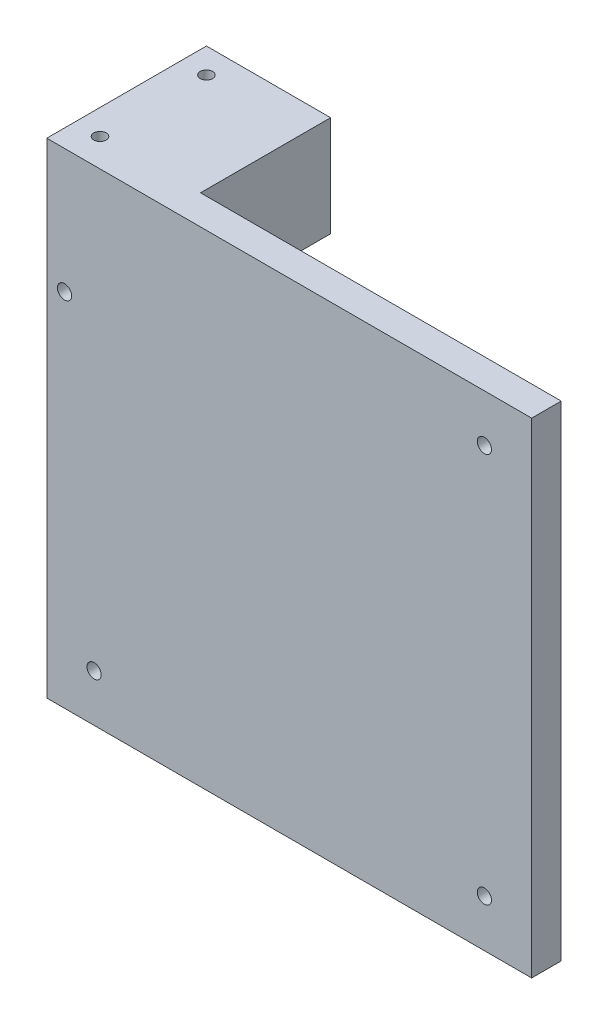
SolidWorks part; units mm, degrees
ref_plane "前基準面" through (0, 0, 0) normal (0, 0, 1) x (1, 0, 0)
ref_plane "上基準面" through (0, 0, 0) normal (0, 1, 0) x (1, 0, 0)
ref_plane "右基準面" through (0, 0, 0) normal (1, 0, 0) x (0, 0, -1)
ref_axis "基準軸1" through (0, -55, 0) along (0, 1, 0)
ref_axis "基準軸2" through (-88.99, 0, 0) along (1, 0, 0)
ref_axis "基準軸3" through (0, 0, 55) along (0, 0, -1)
sketch "草圖1" plane through (0, 0, 0) normal (0, 0, 1) x (1, 0, 0)
  line L0 (0, -55) -> (0, 55) construction
  line L1 (-41, -41) -> (41, -41)
  line L2 (-41, -41) -> (-41, 41)
  line L3 (-41, 41) -> (41, 41)
  line L4 (41, -41) -> (41, 41)
  line L5 (55, 0) -> (-55, 0) construction
  circle A0 centre (0, 0) radius 35.5
  point P7 (0, -41)
  point P10 (41, 0)
  dimension "D1" = 71
  dimension "D2" = 82
  dimension "D3" = 82
extrude "填料-伸長1" add sketch "草圖1" along normal blind 245
sketch "草圖2" plane through (0, 0, 0) normal (0, 0, -1) x (-1, 0, 0)
  line L1 (-41, 41) -> (41, 41)
  line L2 (-41, 41) -> (-41, -41)
  line L3 (-41, -41) -> (41, -41)
  line L4 (41, 41) -> (41, -41)
extrude "填料-伸長2" add sketch "草圖2" along normal blind 27
ref_plane "平面1" through (0, 0, -13.5) normal (0, 0, -1) x (-1, 0, 0)
sketch "草圖3" plane through (0, 0, 245) normal (0, 0, 1) x (1, 0, 0)
  line L0 (-41, 41) -> (-41, -41) construction
  line L1 (-41, 10) -> (-33, 10)
  line L2 (-41, 10) -> (-41, -10)
  line L3 (-41, -10) -> (-33, -10)
  line L4 (-33, 10) -> (-33, -10)
  line L6 (55, 0) -> (-55, 0) construction
  point P6 (-33, 0)
  dimension "D1" = 8
  dimension "D2" = 20
extrude "除料-伸長1" cut sketch "草圖3" against normal up to surface (245 mm away) up to face at (35.5, 0, 0)
sketch "草圖4" plane through (0, 0, 245) normal (0, 0, 1) x (1, 0, 0)
  line L1 (41, 41) -> (-41, 41) construction
  line L2 (-41, 41) -> (-41, 10) construction
  line L3 (-41, -41) -> (41, -41) construction
  line L4 (-41, -10) -> (-41, -41) construction
  circle A0 centre (-32.9, 33) radius 4
  circle A1 centre (33.1, 32.9) radius 4
  circle A2 centre (33, -33.1) radius 4
  circle A3 centre (-33, -33) radius 4
  point P15 (0.05, -0.05)
  dimension "D1" = 8
  dimension "D5" = 8
  dimension "D2" = 8
  dimension "D3" = 8.1
  dimension "D6" = 8
  dimension "D4" = 4
extrude "除料-伸長2" cut sketch "草圖4" against normal blind 20
fillet "圓角2" radius 3 1 edges at (-28.9, 33, 225)
fillet "圓角3" radius 3 1 edges at (37.1, 32.9, 225)
fillet "圓角4" radius 3 1 edges at (-29, -33, 225)
fillet "圓角5" radius 3 1 edges at (37, -33.1, 225)
sketch "草圖5" plane through (0, 41, 0) normal (0, 1, 0) x (1, 0, 0)
  line L0 (-41, -245) -> (-41, 27) construction
  line L4 (-41, 27) -> (41, 27) construction
  circle A2 centre (-36.75, 22.75) radius 1.05
  circle A3 centre (-36.75, 4.75) radius 1.05
  dimension "D1" = 18
  dimension "D2" = 2.1
  dimension "D3" = 2.1
  dimension "D4" = 4.25
  dimension "D5" = 4.25
  dimension "D6" = 4.25
extrude "除料-伸長3" cut sketch "草圖5" against normal blind 10
ref_plane "平面2" through (0, 35, 0) normal (0, 1, 0) x (1, 0, 0)
sketch "草圖6" plane through (0, 35, 0) normal (0, 1, 0) x (1, 0, 0)
  circle A0 centre (-36.75, 22.75) radius 1.05
  circle A1 centre (-36.75, 4.75) radius 1.05
  dimension "D1" = 2.1
  dimension "D2" = 2.1
extrude "填料-伸長3" add sketch "草圖6" along normal blind 0.2
sketch "草圖7" plane through (-41, 0, 0) normal (1, 0, 0) x (0, 0, -1)
  line L1 (27, -41) -> (7, -41)
  line L2 (27, -41) -> (27, 24)
  line L3 (27, 24) -> (7, 24)
  line L4 (7, -41) -> (7, 24)
  dimension "D1" = 20
  dimension "D2" = 65
extrude "除料-伸長5" cut sketch "草圖7" along normal up to next
sketch "草圖8" plane through (0, 41, 0) normal (0, 1, 0) x (1, 0, 0)
  line L0 (0, -45.1) -> (0, 45.1) construction
  line L1 (41, 27) -> (0, 27)
  line L2 (41, 27) -> (41, 7)
  line L3 (41, 7) -> (0, 7)
  line L4 (0, 27) -> (0, 7)
  dimension "D1" = 20
extrude "除料-伸長6" cut sketch "草圖8" against normal up to next
sketch "草圖9" plane through (0, 0, -7) normal (0, 0, -1) x (-1, 0, 0)
  line L0 (-41, -41) -> (-41, 41) construction
  line L1 (-41, -41) -> (41, -41) construction
  line L2 (41, 24) -> (41, -41) construction
  line L3 (0, 41) -> (-41, 41) construction
  line L4 (45.1, 0) -> (-45.1, 0) construction
  circle A0 centre (-33, 33) radius 1.2
  circle A1 centre (-33, -33) radius 1.2
  circle A2 centre (33, -33) radius 1.2
  circle A3 centre (38, 20) radius 1.2
  point P18 (40.1462, 21.8071)
  dimension "D1" = 2.4
  dimension "D2" = 2.4
  dimension "D3" = 2.4
  dimension "D10" = 2.4
  dimension "D4" = 8
  dimension "D5" = 8
  dimension "D6" = 8
  dimension "D7" = 8
  dimension "D8" = 8
  dimension "D9" = 8
  dimension "D11" = 3
  dimension "D12" = 20
extrude "除料-伸長7" cut sketch "草圖9" against normal blind 10
sketch "草圖10" plane through (-41, 0, 0) normal (-1, 0, 0) x (0, 0, 1)
  line L0 (0, -45.1) -> (0, 45.1) construction
  line L1 (0, -41) -> (245, -41)
  line L2 (0, -41) -> (0, 41)
  line L3 (0, 41) -> (245, 41)
  line L4 (245, -41) -> (245, 41)
  line L5 (245, 41) -> (245, 10) construction
  line L6 (245, 41) -> (-27, 41) construction
  line L7 (245, -41) -> (-7, -41) construction
  point P6 (245, 41)
  point P9 (0, 41)
  point P12 (245, -41)
  point P15 (0, -41)
extrude "除料-伸長8" cut sketch "草圖10" against normal up to next
sketch "草圖11" plane through (0, 0, 0) normal (1, 0, 0) x (0, 0, -1)
  line L1 (7, 24) -> (27, 24)
  line L2 (7, 24) -> (7, 41)
  line L3 (7, 41) -> (27, 41)
  line L4 (27, 24) -> (27, 41)
extrude "除料-伸長9" cut sketch "草圖11" against normal blind 20
sketch "草圖12" plane through (0, 0, -7) normal (0, 0, -1) x (-1, 0, 0)
  line L0 (20, 41) -> (20, 24)
  line L1 (41, -41) -> (-41, -41)
  line L2 (41, -41) -> (41, 24)
  line L3 (20, 41) -> (-41, 41)
  line L4 (-41, -41) -> (-41, 41)
  line L5 (20, 24) -> (41, 24) construction
  line L6 (20, 41) -> (20, 24) construction
  line L7 (20, 24) -> (41, 24)
extrude "除料-伸長10" cut sketch "草圖12" against normal blind 2
